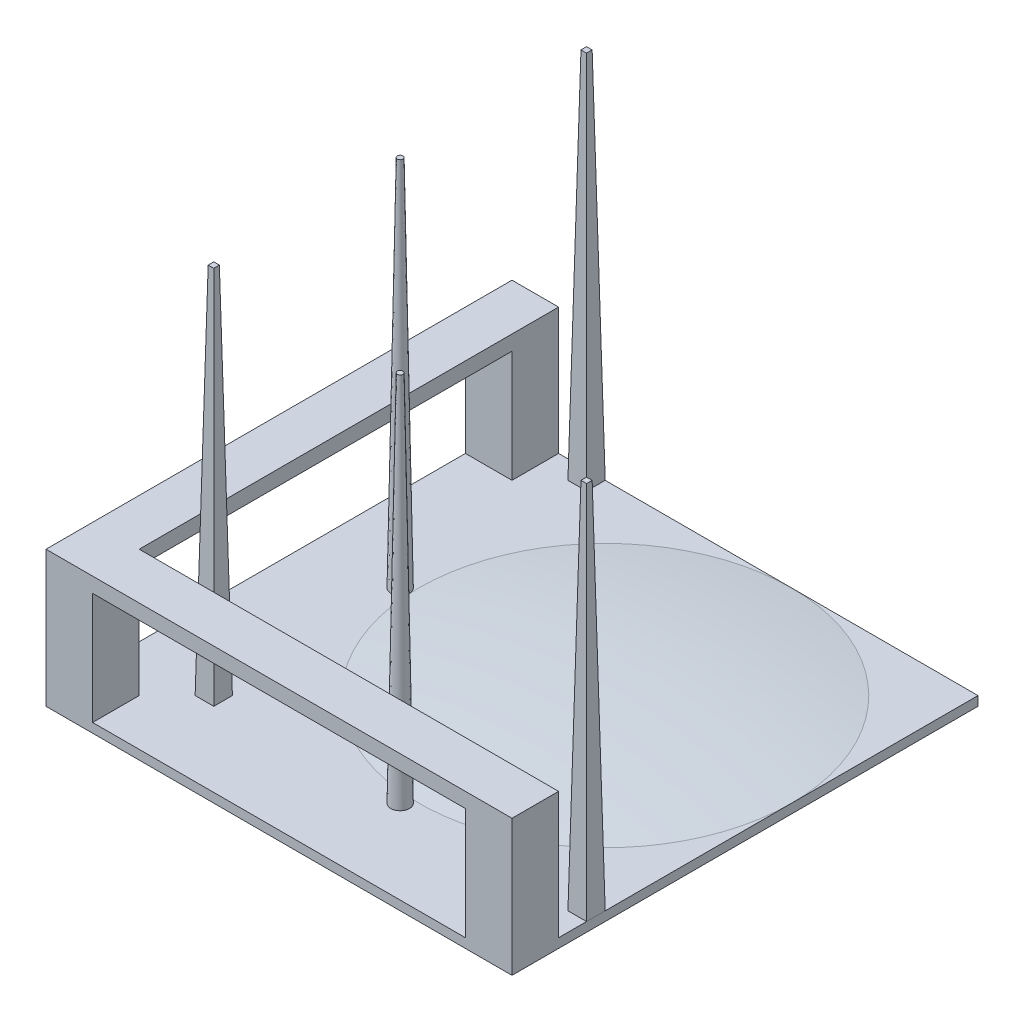
SolidWorks part; units mm, degrees
ref_plane "前视基准面" through (0, 0, 0) normal (0, 0, 1) x (1, 0, 0)
ref_plane "上视基准面" through (0, 0, 0) normal (0, 1, 0) x (1, 0, 0)
ref_plane "右视基准面" through (0, 0, 0) normal (1, 0, 0) x (0, 0, -1)
sketch "草图1" plane through (0, 0, 0) normal (0, 1, 0) x (1, 0, 0)
  line L1 (-20, -20) -> (20, -20)
  line L2 (-20, -20) -> (-20, 20)
  line L3 (-20, 20) -> (20, 20)
  line L4 (20, -20) -> (20, 20)
  line L5 (-20, -20) -> (20, 20) construction
  line L6 (-20, 20) -> (20, -20) construction
  point P0 (0, 0)
  dimension "D1" = 40
  dimension "D2" = 40
extrude "凸台-拉伸1" add sketch "草图1" along normal blind 1
sketch "草图3" plane through (0, 0, 0) normal (0, 0, 1) x (1, 0, 0)
  line L0 (-20, 1) -> (20, 1)
  line L1 (-20, 1) -> (20, 1)
  line L2 (0, 1) -> (0, 2.5) construction
  line L3 (0, 2.5) -> (0, 1)
  arc A0 (0, 2.5) -> (-20, 1) centre (0, -131.5833) ccw
  dimension "D1" = 1.5
revolve "旋转1" add sketch "草图3" angle 360 about L2 region at (-7.5056, 1.6003, 0) other way angle 360
sketch "草图4" plane through (0, 0, 0) normal (0, 1, 0) x (1, 0, 0)
  line L1 (20, -20) -> (-20, -20)
  line L2 (20, -20) -> (20, -22)
  line L3 (20, -22) -> (-20, -22)
  line L4 (20, -20) -> (20, 20)
  line L5 (-20, -20) -> (20, -20)
  line L6 (-20, 20) -> (-20, -20)
  line L7 (20, 20) -> (-20, 20)
  line L8 (20, -20) -> (20, 20)
  line L9 (-20, -20) -> (20, -20)
  line L10 (-20, 20) -> (-20, -20)
  line L11 (20, 20) -> (-20, 20)
  line L12 (-20, -20) -> (-20, -22)
  line L13 (-20, 20) -> (-22, 20)
  line L14 (-20, 20) -> (-20, -22)
  line L15 (-20, -22) -> (-22, -22)
  line L16 (-22, 20) -> (-22, -22)
  dimension "D2" = 2
  dimension "D3" = 2
  dimension "D1" = 0
extrude "凸台-拉伸3" add sketch "草图4" along normal blind 1 contours L1 L12 L3 L2 | L13 L16 L15 L12 L10 region at (0, 0, 21) region at (-21, 0, 1)
sketch "草图5" plane through (0, 1, 0) normal (0, 1, 0) x (1, 0, 0)
  line L0 (-20, 20) -> (-20, -20) construction
  line L1 (20, -20) -> (20, 20) construction
  line L2 (20, 20) -> (-20, 20) construction
  line L3 (-20, 20) -> (-22, 20) construction
  line L4 (-22, 20) -> (-22, -22) construction
  line L5 (-20, -22) -> (-22, -22) construction
  line L6 (-20, 20) -> (-20, -22) construction
  line L7 (20, -20) -> (20, -22) construction
  line L8 (20, -22) -> (-20, -22) construction
  line L9 (-20, -20) -> (-20, -22) construction
  line L10 (20, -20) -> (-20, -20) construction
  line L11 (-20, -20) -> (20, -20) construction
  line L12 (-20, 20) -> (-20, -20)
  line L13 (20, -20) -> (20, 20)
  line L14 (20, 20) -> (-20, 20)
  line L15 (-20, 20) -> (-22, 20)
  line L16 (-22, 20) -> (-22, -22)
  line L17 (-20, -22) -> (-22, -22)
  line L18 (-20, 20) -> (-20, -22)
  line L19 (20, -20) -> (20, -22)
  line L20 (20, -22) -> (-20, -22)
  line L21 (-20, -20) -> (-20, -22)
  line L22 (20, -20) -> (-20, -20)
  line L23 (-20, -20) -> (20, -20)
  line L24 (-20, 0) -> (-22, 0)
  line L25 (18, -20) -> (20, -20)
  line L26 (18, -20) -> (18, -22)
  line L27 (18, -22) -> (20, -22)
  line L28 (20, -20) -> (20, -22)
  line L29 (18, -20) -> (20, -22) construction
  line L30 (18, -22) -> (20, -20) construction
  line L31 (-20, 18) -> (-22, 18)
  line L32 (-20, 18) -> (-20, 20)
  line L33 (-20, 20) -> (-22, 20)
  line L34 (-22, 18) -> (-22, 20)
  line L35 (-20, 18) -> (-22, 20) construction
  line L36 (-20, 20) -> (-22, 18) construction
  line L37 (-20, -2) -> (-22, -2)
  line L38 (-20, -2) -> (-20, 0)
  line L39 (-20, 0) -> (-22, 0)
  line L40 (-22, -2) -> (-22, 0)
  line L41 (-20, -2) -> (-22, 0) construction
  line L42 (-20, 0) -> (-22, -2) construction
  line L43 (-20, -20) -> (-22, -20)
  line L44 (-20, -22) -> (-22, -22)
  line L45 (-20, -22) -> (-20, -20)
  line L46 (-20, -20) -> (-22, -20)
  line L47 (-22, -22) -> (-22, -20)
  line L48 (-20, -22) -> (-22, -20) construction
  line L49 (-20, -20) -> (-22, -22) construction
  line L50 (0, -20) -> (0, -22)
  line L51 (-2, -20) -> (0, -20)
  line L52 (-2, -20) -> (-2, -22)
  line L53 (-2, -22) -> (0, -22)
  line L54 (0, -20) -> (0, -22)
  line L55 (-2, -20) -> (0, -22) construction
  line L56 (-2, -22) -> (0, -20) construction
  point P7 (19, -21)
  point P9 (-21, 19)
  point P19 (-21, -1)
  point P25 (-21, -21)
  point P30 (-1, -21)
  line M8 (0, 20) -> (-22, 20)
  line M9 (-22, 20) -> (-22, -22)
  line M10 (-22, -22) -> (20, -22)
  line M11 (20, -22) -> (20, 0)
  dimension "D1" = 2
  dimension "D2" = 2
  dimension "D3" = 2
  dimension "D4" = 3
  dimension "D5" = 2
extrude "凸台-拉伸4" add sketch "草图5" along normal blind 40 contours L22 L26 L20 M11 | L31 L12 M8 M9 | L22 L52 L20 L50 | L18 L43 L16 M10 | L37 L12 L24 L16 region at (-21, 1, -19) region at (-21, 1, 1) region at (-21, 1, 21) region at (19, 1, 21) region at (-1, 1, 21)
sketch "草图6" plane through (0, 41, 0) normal (0, 1, 0) x (1, 0, 0)
  line L4 (-22, -2) -> (-20, -2)
  line L5 (-20, -2) -> (-20, 0)
  line L6 (-20, 0) -> (-22, 0)
  line L7 (-22, 0) -> (-22, -2)
  line L8 (-22, -2) -> (-20, -2)
  line L10 (-20, 0) -> (-22, 0)
  line L11 (-22, 0) -> (-22, -2)
  line L12 (0, -20) -> (-2, -20)
  line L13 (-2, -20) -> (-2, -22)
  line L14 (-2, -22) -> (0, -22)
  line L15 (0, -22) -> (0, -20)
  line L16 (0, -20) -> (-2, -20)
  line L17 (-2, -20) -> (-2, -22)
  line L18 (-2, -22) -> (0, -22)
  line L19 (0, -22) -> (0, -20)
  line L21 (-20, -2) -> (-20, 0)
  circle A0 centre (-21, -1) radius 1
  circle A1 centre (-1, -21) radius 1
  line M10 (-22, -2) -> (-20, -2)
  line M11 (-20, -2) -> (-20, 0)
  line M12 (-20, 0) -> (-22, 0)
  line M13 (-22, 0) -> (-22, -2)
  dimension "D1" = 0
  dimension "D2" = 0
extrude "切除-拉伸1" cut sketch "草图6" against normal blind 40 contours A0 L8 M11 | A0 L11 M10 | A0 L10 M13 | A0 L21 M12 | A1 L19 L16 | A1 L18 L19 | A1 L17 L18 | A1 L16 L17 region at (-21.7766, 41, 1.7766) region at (-20.2234, 41, 1.7766) region at (-21.7766, 41, 0.2234) region at (-20.2234, 41, 0.2234) region at (-0.2234, 41, 20.2234) region at (-1.7766, 41, 20.2234) region at (-0.2234, 41, 21.7766) region at (-1.7766, 41, 21.7766)
chamfer "倒角1" distance 40 distance2 0.7 2 edges at (-1, 41, 22) (-21, 41, 2) first distance on face at (-1, 41, 22) first distance on face at (-21, 41, 2)
chamfer "倒角2" distance 40 distance2 0.7 4 edges at (20, 41, 21) (19, 41, 22) (18, 41, 21) (19, 41, 20) first distance on face at (20, 12.1429, 6.2857) first distance on face at (-1, 18.5556, 22) first distance on face at (18, 21, 21) first distance on face at (19, 21, 20)
chamfer "倒角3" distance 0.7 distance2 40 4 edges at (-21, 41, 22) (-22, 41, 21) (-21, 41, 20) (-20, 41, 21) first distance on face at (-21, 41, 21)
chamfer "倒角4" distance 0.7 distance2 40 4 edges at (-22, 41, -19) (-21, 41, -20) (-21, 41, -18) (-20, 41, -19) first distance on face at (-21, 41, -19)
sketch "草图7" plane through (0, 0, 0) normal (0, -1, 0) x (1, 0, 0)
  line L1 (20, -20) -> (-30, -20)
  line L2 (20, -20) -> (20, 30)
  line L3 (20, 30) -> (-30, 30)
  line L4 (20, -20) -> (20, 22)
  line L5 (20, 22) -> (-22, 22)
  line L6 (-22, 22) -> (-22, -20)
  line L7 (-22, -20) -> (20, -20)
  line L8 (20, -20) -> (20, 22)
  line L9 (20, 22) -> (-22, 22)
  line L10 (-22, 22) -> (-22, -20)
  line L11 (-22, -20) -> (20, -20)
  line L12 (-30, -20) -> (-30, 30)
  line M8 (20, 22) -> (-22, 22)
  line M9 (-22, 22) -> (-22, -20)
  dimension "D2" = 50
  dimension "D3" = 50
  dimension "D1" = 0
extrude "凸台-拉伸5" add sketch "草图7" against normal blind 1 contours L12 L1 L2 L3 M9 M8 region at (-26, 0, -19.2929)
sketch "草图8" plane through (0, 1, 0) normal (0, 1, 0) x (1, 0, 0)
  line L0 (-30, -25) -> (20, -25)
  line L1 (-25, 20) -> (-25, -30)
  line L2 (-22, 15) -> (-30, 15)
  line L3 (15, -30) -> (15, -22)
  line L12 (20, -22) -> (18, -22)
  line L13 (18, -22) -> (18, -20)
  line L14 (18, -20) -> (20, -20)
  line L15 (20, -20) -> (20, 0)
  line L16 (0, 20) -> (-20, 20)
  line L17 (-20, 20) -> (-20, 18)
  line L18 (-20, 18) -> (-22, 18)
  line L19 (-22, 18) -> (-22, 20)
  line L20 (-22, 20) -> (-30, 20)
  line L21 (-30, 20) -> (-30, -30)
  line L22 (-30, -30) -> (20, -30)
  line L23 (20, -30) -> (20, -22)
  line L24 (20, -22) -> (18, -22)
  line L25 (18, -22) -> (18, -20)
  line L26 (18, -20) -> (20, -20)
  line L27 (20, -20) -> (20, 0)
  line L28 (0, 20) -> (-20, 20)
  line L29 (-20, 20) -> (-20, 18)
  line L30 (-20, 18) -> (-22, 18)
  line L31 (-22, 18) -> (-22, 20)
  line L32 (-22, 20) -> (-30, 20)
  line L33 (-30, 20) -> (-30, -30)
  line L34 (-30, -30) -> (20, -30)
  line L35 (20, -30) -> (20, -22)
  arc A1 (0, 20) -> (20, 0) centre (0, 0) ccw
  arc A2 (0, 20) -> (20, 0) centre (0, 0) ccw
  line M28 (-22, 20) -> (-30, 20)
  line M29 (-30, 20) -> (-30, -30)
  line M30 (-30, -30) -> (20, -30)
  line M31 (20, -30) -> (20, -22)
  dimension "D1" = 0
  dimension "D2" = 5
  dimension "D3" = 5
  dimension "D4" = 5
  dimension "D5" = 5
extrude "凸台-拉伸6" add sketch "草图8" along normal blind 12 contours L1 L0 M29 M30 | L3 L0 M30 M31 | L2 L1 M28 M29 region at (-27.5, 1, 27.5) region at (-27.5, 1, -17.5) region at (17.5, 1, 27.5)
sketch "草图9" plane through (0, 1, 0) normal (0, 1, 0) x (1, 0, 0)
  line L0 (-10, -30) -> (-10, -25)
  line L1 (-10, -25) -> (-15, -25)
  line L2 (-15, -25) -> (-15, -30)
  line L3 (-15, -30) -> (-10, -30)
  line L4 (-25, -30) -> (-25, -25)
  line L5 (-25, -25) -> (-30, -25)
  line L6 (-30, -25) -> (-30, -30)
  line L7 (-30, -30) -> (-25, -30)
  line L8 (-25, -30) -> (-25, -25)
  line L9 (-25, -25) -> (-30, -25)
  line L10 (-30, -25) -> (-30, -30)
  line L11 (-30, -30) -> (-25, -30)
  line L12 (-10, -15) -> (-10, -10)
  line L13 (-10, -10) -> (-15, -10)
  line L14 (-15, -10) -> (-15, -15)
  line L15 (-15, -15) -> (-10, -15)
  line L16 (-25, -15) -> (-25, -10)
  line L17 (-25, -10) -> (-30, -10)
  line L18 (-30, -10) -> (-30, -15)
  line L19 (-30, -15) -> (-25, -15)
  line M20 (-30, 15) -> (-30, -25)
  line M23 (-25, -30) -> (15, -30)
  dimension "D1" = 0
  dimension "D2" = 2
  dimension "D3" = 2
extrude "凸台-拉伸7" [suppressed] add sketch "草图9" along normal blind 1 contours L19 L16 L17 M20 | L1 L2 L0 M23
sketch "草图10" [suppressed] plane through (0, 2, 0) normal (0, 1, 0) x (1, 0, 0)
  line L4 (-20, -35) -> (-25, -35)
  line L5 (-25, -35) -> (-25, -40)
  line L6 (-25, -40) -> (-20, -40)
  line L7 (-20, -40) -> (-20, -35)
  line L8 (-20, -35) -> (-35, -35)
  line L9 (-25, -35) -> (-25, -40)
  line L10 (-35, -40) -> (-20, -40)
  line L11 (-20, -40) -> (-20, -35)
  line L12 (-40, -20) -> (-40, -25)
  line L13 (-40, -25) -> (-35, -25)
  line L14 (-35, -25) -> (-35, -20)
  line L15 (-35, -20) -> (-40, -20)
  line L16 (-40, -20) -> (-40, -25)
  line L17 (-40, -25) -> (-35, -25)
  line L18 (-35, -25) -> (-35, -20)
  line L19 (-35, -20) -> (-40, -20)
  line L20 (-35, -40) -> (-35, -35)
  line L21 (-35, -35) -> (-40, -35)
  line L22 (-40, -35) -> (-40, -40)
  line L23 (-40, -40) -> (-35, -40)
  line L24 (-35, -40) -> (-35, -25)
  line L25 (-35, -35) -> (-40, -35)
  line L26 (-40, -25) -> (-40, -40)
  line L27 (-40, -40) -> (-35, -40)
  line M13 (-20, -35) -> (-25, -35)
  line M14 (-25, -35) -> (-25, -40)
  line M15 (-25, -40) -> (-20, -40)
  line M16 (-20, -40) -> (-20, -35)
  dimension "D1" = 0
  dimension "D2" = 0
  dimension "D3" = 0
extrude "凸台-拉伸8" [suppressed] add sketch "草图10" along normal blind 2 contours L18 L19 L16 L17 | L17 L26 L25 L24 | L26 L27 L24 L25 | L24 L10 L8 M14 | M16 M13 M14 M15
sketch "草图11" [suppressed] plane through (0, 1, 0) normal (0, 1, 0) x (1, 0, 0)
  line L20 (-15, -40) -> (-15, -35)
  line L21 (-15, -35) -> (-20, -35)
  line L22 (-20, -35) -> (-20, -40)
  line L23 (-20, -40) -> (-15, -40)
  line L24 (-20, -25) -> (-20, -20)
  line L25 (-20, -20) -> (-25, -20)
  line L26 (-25, -20) -> (-25, -25)
  line L27 (-25, -25) -> (-20, -25)
  line L28 (-20, -25) -> (-20, -20)
  line L29 (-20, -20) -> (-25, -20)
  line L30 (-25, -20) -> (-25, -25)
  line L31 (-25, -25) -> (-20, -25)
  line L32 (-35, -40) -> (-35, -35)
  line L33 (-35, -35) -> (-40, -35)
  line L34 (-40, -35) -> (-40, -40)
  line L35 (-40, -40) -> (-35, -40)
  line L36 (-35, -40) -> (-35, -35)
  line L37 (-35, -35) -> (-40, -35)
  line L38 (-40, -35) -> (-40, -40)
  line L39 (-40, -40) -> (-35, -40)
  line L52 (-20, -40) -> (-20, -35)
  line L53 (-20, -35) -> (-25, -35)
  line L54 (-25, -35) -> (-25, -40)
  line L55 (-25, -40) -> (-20, -40)
  line L56 (-20, -40) -> (-20, -35)
  line L57 (-20, -35) -> (-25, -35)
  line L58 (-25, -35) -> (-25, -40)
  line L59 (-25, -40) -> (-20, -40)
  line L60 (-35, -20) -> (-40, -20)
  line L61 (-40, -20) -> (-40, -25)
  line L62 (-40, -25) -> (-35, -25)
  line L63 (-35, -25) -> (-35, -20)
  line L64 (-35, -20) -> (-40, -20)
  line L65 (-40, -20) -> (-40, -25)
  line L66 (-40, -25) -> (-35, -25)
  line L67 (-35, -25) -> (-35, -20)
  line L68 (-15, -20) -> (-15, -15)
  line L69 (-15, -15) -> (-20, -15)
  line L70 (-20, -15) -> (-20, -20)
  line L71 (-20, -20) -> (-15, -20)
  line L72 (-35, -20) -> (-35, -15)
  line L73 (-35, -15) -> (-40, -15)
  line L74 (-40, -15) -> (-40, -20)
  line L75 (-40, -20) -> (-35, -20)
  line L76 (-40, -40) -> (-20, -40) construction
  line L77 (-40, -25) -> (-40, -35) construction
  line M39 (-20, -40) -> (15, -40)
  line M55 (-40, 15) -> (-40, -20)
  dimension "D7" = 20
  dimension "D8" = 20
  dimension "D1" = 0
  dimension "D2" = 0
  dimension "D3" = 0
  dimension "D4" = 0
  dimension "D5" = 2
  dimension "D6" = 2
extrude "凸台-拉伸9" [suppressed] add sketch "草图11" along normal blind 4 contours L75 L72 L73 M55 | L21 L22 L20 M39 | L36 L37 L38 L39
sketch "草图12" [suppressed] plane through (0, 5, 0) normal (0, 1, 0) x (1, 0, 0)
  line L4 (-40, -40) -> (-35, -40)
  line L5 (-35, -40) -> (-35, -35)
  line L6 (-35, -35) -> (-40, -35)
  line L7 (-40, -35) -> (-40, -40)
  line L8 (-40, -40) -> (-35, -40)
  line L9 (-35, -40) -> (-35, -35)
  line L10 (-35, -35) -> (-40, -35)
  line L11 (-40, -35) -> (-40, -40)
  line L12 (-15, -35) -> (-20, -35)
  line L13 (-20, -35) -> (-20, -40)
  line L14 (-20, -40) -> (-15, -40)
  line L15 (-15, -40) -> (-15, -35)
  line L16 (-15, -35) -> (-35, -35)
  line L17 (-20, -35) -> (-20, -40)
  line L18 (-35, -40) -> (-15, -40)
  line L19 (-15, -40) -> (-15, -35)
  line L20 (-40, -15) -> (-40, -20)
  line L21 (-40, -20) -> (-35, -20)
  line L22 (-35, -20) -> (-35, -15)
  line L23 (-35, -15) -> (-40, -15)
  line L24 (-40, -15) -> (-40, -35)
  line L25 (-40, -20) -> (-35, -20)
  line L26 (-35, -35) -> (-35, -15)
  line L27 (-35, -15) -> (-40, -15)
  line M13 (-40, -40) -> (-35, -40)
  line M14 (-35, -40) -> (-35, -35)
  line M15 (-35, -35) -> (-40, -35)
  line M16 (-40, -35) -> (-40, -40)
  dimension "D1" = 0
  dimension "D2" = 0
  dimension "D3" = 0
extrude "凸台-拉伸10" [suppressed] add sketch "草图12" along normal blind 2 contours L18 L19 L16 L17 | L18 L17 L16 M14 | M16 M13 M14 M15 | L26 L25 L24 M15 | L26 L27 L24 L25
sketch "草图13" plane through (0, 1, 0) normal (0, 1, 0) x (1, 0, 0)
  line L0 (0, -30) -> (0, -25)
  line L1 (0, -25) -> (-5, -25)
  line L2 (-5, -25) -> (-5, -30)
  line L3 (-5, -30) -> (0, -30)
  line L4 (-10, -15) -> (-10, -10)
  line L5 (-10, -10) -> (-15, -10)
  line L6 (-15, -10) -> (-15, -15)
  line L7 (-15, -15) -> (-10, -15)
  line L8 (-10, -15) -> (-10, -10)
  line L9 (-10, -10) -> (-15, -10)
  line L10 (-15, -10) -> (-15, -15)
  line L11 (-15, -15) -> (-10, -15)
  line L12 (-25, -30) -> (-25, -25)
  line L13 (-25, -25) -> (-30, -25)
  line L14 (-30, -25) -> (-30, -30)
  line L15 (-30, -30) -> (-25, -30)
  line L16 (-25, -30) -> (-25, -25)
  line L17 (-25, -25) -> (-30, -25)
  line L18 (-30, -25) -> (-30, -30)
  line L19 (-30, -30) -> (-25, -30)
  line L20 (-10, -30) -> (-10, -25)
  line L21 (-10, -25) -> (-15, -25)
  line L22 (-15, -25) -> (-15, -30)
  line L23 (-15, -30) -> (-10, -30)
  line L24 (-10, -30) -> (-10, -25)
  line L25 (-10, -25) -> (-15, -25)
  line L26 (-15, -25) -> (-15, -30)
  line L27 (-15, -30) -> (-10, -30)
  line L28 (-25, -10) -> (-30, -10)
  line L29 (-30, -10) -> (-30, -15)
  line L30 (-30, -15) -> (-25, -15)
  line L31 (-25, -15) -> (-25, -10)
  line L32 (-25, -10) -> (-30, -10)
  line L33 (-30, -10) -> (-30, -15)
  line L34 (-30, -15) -> (-25, -15)
  line L35 (-25, -15) -> (-25, -10)
  line L36 (0, -5) -> (0, 0)
  line L37 (0, 0) -> (-5, 0)
  line L38 (-5, 0) -> (-5, -5)
  line L39 (-5, -5) -> (0, -5)
  line L40 (-25, -5) -> (-25, 0)
  line L41 (-25, 0) -> (-30, 0)
  line L42 (-30, 0) -> (-30, -5)
  line L43 (-30, -5) -> (-25, -5)
  dimension "D1" = 0
  dimension "D2" = 0
  dimension "D3" = 0
  dimension "D4" = 0
  dimension "D5" = 2
  dimension "D6" = 2
extrude "凸台-拉伸11" [suppressed] add sketch "草图13" along normal blind 7
sketch "草图14" [suppressed] plane through (0, 8, 0) normal (0, 1, 0) x (1, 0, 0)
  line L4 (-35, -15) -> (-35, -10)
  line L5 (-35, -10) -> (-40, -10)
  line L6 (-40, -10) -> (-40, -15)
  line L7 (-40, -15) -> (-35, -15)
  line L8 (-35, -35) -> (-35, -10)
  line L9 (-35, -10) -> (-40, -10)
  line L10 (-40, -10) -> (-40, -35)
  line L11 (-40, -15) -> (-35, -15)
  line L12 (-40, -35) -> (-40, -40)
  line L13 (-40, -40) -> (-35, -40)
  line L14 (-35, -40) -> (-35, -35)
  line L15 (-35, -35) -> (-40, -35)
  line L16 (-40, -35) -> (-40, -40)
  line L17 (-40, -40) -> (-35, -40)
  line L18 (-35, -40) -> (-35, -35)
  line L19 (-35, -35) -> (-40, -35)
  line L20 (-10, -40) -> (-10, -35)
  line L21 (-10, -35) -> (-15, -35)
  line L22 (-15, -35) -> (-15, -40)
  line L23 (-15, -40) -> (-10, -40)
  line L24 (-10, -40) -> (-10, -35)
  line L25 (-10, -35) -> (-35, -35)
  line L26 (-15, -35) -> (-15, -40)
  line L27 (-35, -40) -> (-10, -40)
  line M13 (-35, -15) -> (-35, -10)
  line M14 (-35, -10) -> (-40, -10)
  line M15 (-40, -10) -> (-40, -15)
  line M16 (-40, -15) -> (-35, -15)
  dimension "D1" = 0
  dimension "D2" = 0
  dimension "D3" = 0
extrude "凸台-拉伸12" [suppressed] add sketch "草图14" along normal blind 2 contours M16 M13 M14 M15 | L19 L8 L10 M16 | L18 L19 L16 L17 | L18 L27 L26 L25 | L26 L27 L24 L25
sketch "草图15" plane through (0, 1, 0) normal (0, 1, 0) x (1, 0, 0)
  line L0 (5, -30) -> (5, -25)
  line L1 (5, -25) -> (0, -25)
  line L2 (0, -25) -> (0, -30)
  line L3 (0, -30) -> (5, -30)
  line L4 (-10, -15) -> (-10, -10)
  line L5 (-10, -10) -> (-15, -10)
  line L6 (-15, -10) -> (-15, -15)
  line L7 (-15, -15) -> (-10, -15)
  line L8 (-10, -15) -> (-10, -10)
  line L9 (-10, -10) -> (-15, -10)
  line L10 (-15, -10) -> (-15, -15)
  line L11 (-15, -15) -> (-10, -15)
  line L12 (-25, -30) -> (-25, -25)
  line L13 (-25, -25) -> (-30, -25)
  line L14 (-30, -25) -> (-30, -30)
  line L15 (-30, -30) -> (-25, -30)
  line L16 (-25, -30) -> (-25, -25)
  line L17 (-25, -25) -> (-30, -25)
  line L18 (-30, -25) -> (-30, -30)
  line L19 (-30, -30) -> (-25, -30)
  line L20 (-10, -30) -> (-10, -25)
  line L21 (-10, -25) -> (-15, -25)
  line L22 (-15, -25) -> (-15, -30)
  line L23 (-15, -30) -> (-10, -30)
  line L24 (-10, -30) -> (-10, -25)
  line L25 (-10, -25) -> (-15, -25)
  line L26 (-15, -25) -> (-15, -30)
  line L27 (-15, -30) -> (-10, -30)
  line L28 (-25, -10) -> (-30, -10)
  line L29 (-30, -10) -> (-30, -15)
  line L30 (-30, -15) -> (-25, -15)
  line L31 (-25, -15) -> (-25, -10)
  line L32 (-25, -10) -> (-30, -10)
  line L33 (-30, -10) -> (-30, -15)
  line L34 (-30, -15) -> (-25, -15)
  line L35 (-25, -15) -> (-25, -10)
  line L36 (5, 0) -> (5, 5)
  line L37 (5, 5) -> (0, 5)
  line L38 (0, 5) -> (0, 0)
  line L39 (0, 0) -> (5, 0)
  line L40 (-25, 0) -> (-25, 5)
  line L41 (-25, 5) -> (-30, 5)
  line L42 (-30, 5) -> (-30, 0)
  line L43 (-30, 0) -> (-25, 0)
  dimension "D1" = 0
  dimension "D2" = 0
  dimension "D3" = 0
  dimension "D4" = 0
  dimension "D5" = 2
  dimension "D6" = 2
extrude "凸台-拉伸13" [suppressed] add sketch "草图15" along normal blind 10
sketch "草图16" [suppressed] plane through (0, 11, 0) normal (0, 1, 0) x (1, 0, 0)
  line L4 (-35, -10) -> (-35, -5)
  line L5 (-35, -5) -> (-40, -5)
  line L6 (-40, -5) -> (-40, -10)
  line L7 (-40, -10) -> (-35, -10)
  line L8 (-35, -10) -> (-35, -5)
  line L9 (-35, -5) -> (-40, -5)
  line L10 (-40, -5) -> (-40, -10)
  line L11 (-40, -10) -> (-35, -10)
  line L12 (-40, -35) -> (-40, -40)
  line L13 (-40, -40) -> (-35, -40)
  line L14 (-35, -40) -> (-35, -35)
  line L15 (-35, -35) -> (-40, -35)
  line L16 (-40, -35) -> (-40, -40)
  line L17 (-40, -40) -> (-35, -40)
  line L18 (-35, -40) -> (-35, -35)
  line L19 (-35, -35) -> (-40, -35)
  line L20 (-5, -40) -> (-5, -35)
  line L21 (-5, -35) -> (-10, -35)
  line L22 (-10, -35) -> (-10, -40)
  line L23 (-10, -40) -> (-5, -40)
  line L24 (-5, -40) -> (-5, -35)
  line L25 (-5, -35) -> (-10, -35)
  line L26 (-10, -35) -> (-10, -40)
  line L27 (-10, -40) -> (-5, -40)
  dimension "D1" = 0
  dimension "D2" = 0
  dimension "D3" = 0
sketch "草图17" plane through (0, 13, 0) normal (0, 1, 0) x (1, 0, 0)
  line L4 (-30, 15) -> (-25, 15)
  line L5 (-25, 15) -> (-25, 20)
  line L6 (-25, 20) -> (-30, 20)
  line L7 (-30, 20) -> (-30, 15)
  line L8 (-30, 15) -> (-25, 15)
  line L9 (-25, -25) -> (-25, 20)
  line L10 (-25, 20) -> (-30, 20)
  line L11 (-30, 20) -> (-30, -25)
  line L12 (-25, -30) -> (-25, -25)
  line L13 (-25, -25) -> (-30, -25)
  line L14 (-30, -25) -> (-30, -30)
  line L15 (-30, -30) -> (-25, -30)
  line L16 (-25, -30) -> (-25, -25)
  line L17 (-25, -25) -> (-30, -25)
  line L18 (-30, -25) -> (-30, -30)
  line L19 (-30, -30) -> (-25, -30)
  line L20 (15, -25) -> (15, -30)
  line L21 (15, -30) -> (20, -30)
  line L22 (20, -30) -> (20, -25)
  line L23 (20, -25) -> (15, -25)
  line L24 (15, -25) -> (15, -30)
  line L25 (-25, -30) -> (20, -30)
  line L26 (20, -30) -> (20, -25)
  line L27 (20, -25) -> (-25, -25)
  line M13 (-30, 15) -> (-25, 15)
  line M14 (-25, 15) -> (-25, 20)
  line M15 (-25, 20) -> (-30, 20)
  line M16 (-30, 20) -> (-30, 15)
  dimension "D1" = 0
  dimension "D2" = 0
  dimension "D3" = 0
extrude "凸台-拉伸14" add sketch "草图17" along normal blind 1.6 contours M16 M13 M14 M15 | L17 L9 L11 M13 | L18 L19 L16 L17 | L24 L27 L16 L25 | L26 L27 L24 L25 region at (-27.5, 13, -17.5) region at (-27.5, 13, 5) region at (-27.5, 13, 27.5) region at (-5, 13, 27.5) region at (17.5, 13, 27.5)
